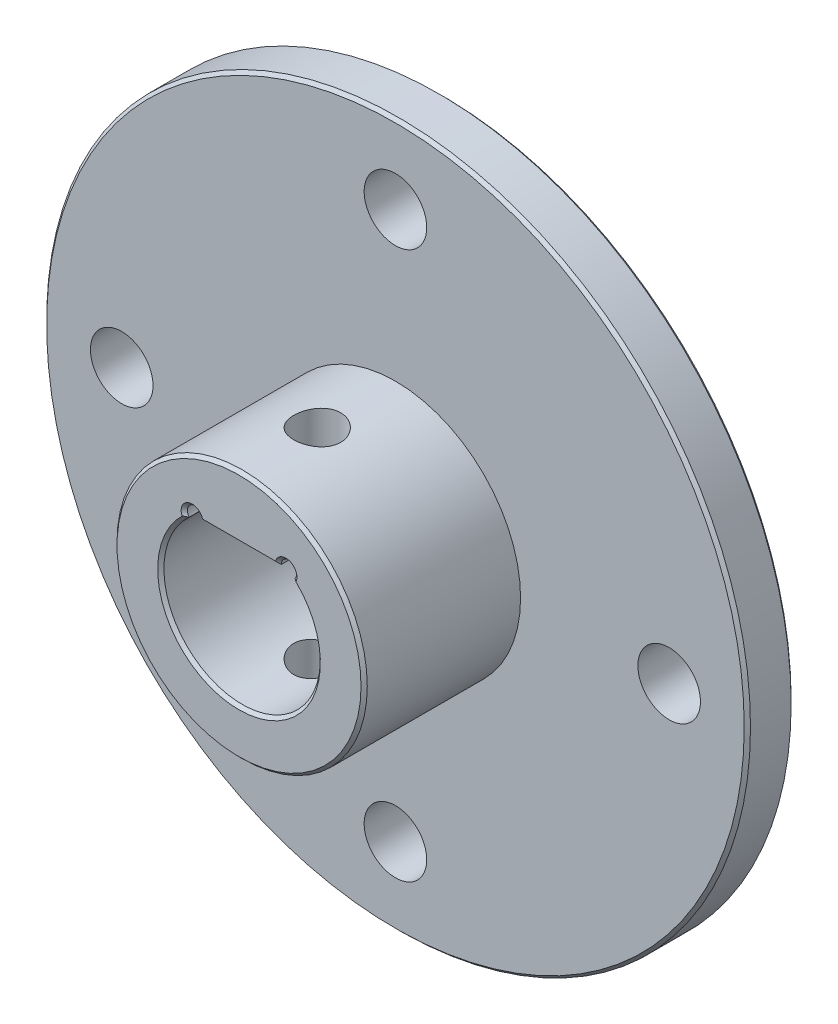
SolidWorks part; units mm, degrees
ref_plane "前视基准面" through (0, 0, 0) normal (0, 0, 1) x (1, 0, 0)
ref_plane "上视基准面" through (0, 0, 0) normal (0, 1, 0) x (1, 0, 0)
ref_plane "右视基准面" through (0, 0, 0) normal (1, 0, 0) x (0, 0, -1)
sketch "草图1" plane through (0, 0, 0) normal (0, 0, 1) x (1, 0, 0)
  line L0 (0, 43.1167) -> (0, -36.0758) construction
  line L1 (-52.3703, 0) -> (56.6741, 0) construction
  line L2 (2.5, 4) -> (-3, 4)
  circle A0 centre (0, 0) radius 22.5
  circle A1 centre (0, 0) radius 17.5 construction
  circle A2 centre (0, 17.5) radius 2
  circle A3 centre (17.5, 0) radius 2
  circle A4 centre (0, -17.5) radius 2
  circle A5 centre (-17.5, 0) radius 2
  arc A6 (-3.3845, 3.6804) -> (3.3845, 3.6804) centre (0, 0) ccw
  arc A7 (-2.5, 4) -> (-3.3845, 3.6804) centre (-3, 4) ccw
  arc A8 (2.5, 4) -> (3.3845, 3.6804) centre (3, 4) cw
  dimension "D1" = 35
  dimension "D2" = 45
  dimension "D3" = 4
  dimension "D5" = 10
  dimension "D6" = 1
  dimension "D7" = 4
  dimension "D4" = 4
extrude "凸台-拉伸1" add sketch "草图1" along normal blind 3 contours A0 A5 A4 A3 A2 L2 A8 A6 A7 region at (-21.8636, 0, 0)
sketch "草图2" plane through (0, 0, 3) normal (0, 0, 1) x (1, 0, 0)
  line L0 (2.5, 4) -> (-2.5, 4) construction
  line L1 (2.5, 4) -> (-2.5, 4)
  circle A0 centre (0, 0) radius 8
  arc A1 (-2.5, 4) -> (-3.3845, 3.6804) centre (-3, 4) ccw construction
  arc A2 (-3.3845, 3.6804) -> (3.3845, 3.6804) centre (0, 0) ccw construction
  arc A3 (3.3845, 3.6804) -> (2.5, 4) centre (3, 4) ccw construction
  arc A4 (3.3845, 3.6804) -> (2.5, 4) centre (3, 4) ccw
  arc A5 (-3.3845, 3.6804) -> (3.3845, 3.6804) centre (0, 0) ccw
  arc A6 (-2.5, 4) -> (-3.3845, 3.6804) centre (-3, 4) ccw
  dimension "D1" = 16
extrude "凸台-拉伸2" add sketch "草图2" along normal blind 10
chamfer "倒角1" distance 0.2 angle 45 7 edges at (0, -5, 13) (3.1699, 4.4702, 13) (-3.1699, 4.4702, 13) (0, 4, 13) (8, 0, 13) (22.5, 0, 0) (22.5, 0, 3)
sketch "草图3" plane through (0, 0, 0) normal (0, 1, 0) x (1, 0, 0)
  line L0 (2, 0) -> (-2, 0) construction
  circle A0 centre (0, -8) radius 1.5
  dimension "D1" = 3
  dimension "D2" = 8
extrude "切除-拉伸1" cut sketch "草图3" against normal through all both and the other way through all
